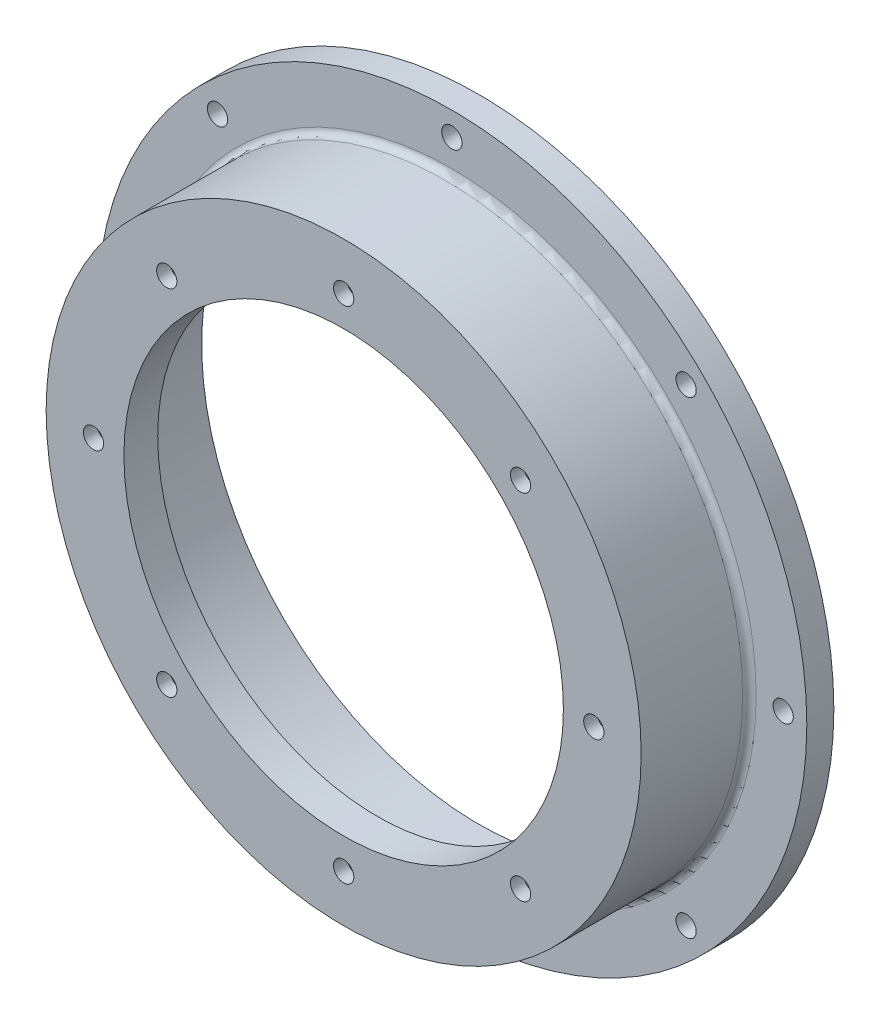
SolidWorks part; units mm, degrees
material "1.0503 (C45)"
ref_plane "Front Plane" through (0, 0, 0) normal (0, 0, 1) x (1, 0, 0)
ref_plane "Top Plane" through (0, 0, 0) normal (0, 1, 0) x (1, 0, 0)
ref_plane "Right Plane" through (0, 0, 0) normal (1, 0, 0) x (0, 0, -1)
sketch "Sketch1" plane through (0, 0, 0) normal (0, 0, 1) x (1, 0, 0)
  line L0 (0, 0) -> (0, 63.1981) construction
  circle A0 centre (0, 0) radius 52.5
  circle A1 centre (0, 0) radius 32.5
  circle A2 centre (0, 0) radius 41
  circle A3 centre (0, 0) radius 44
  point P2 (0, 49)
  point P3 (0, 37)
  point P5 (26.163, 26.163)
  point P6 (34.6482, 34.6482)
  point P8 (37, 0)
  point P9 (26.163, -26.163)
  point P10 (0, -37)
  point P11 (-26.163, -26.163)
  point P12 (-37, 0)
  point P13 (-26.163, 26.163)
  point P14 (0, 0)
  point P17 (49, 0)
  point P18 (34.6482, -34.6482)
  point P19 (0, -49)
  point P20 (-34.6482, -34.6482)
  point P21 (-49, 0)
  point P22 (-34.6482, 34.6482)
  point P23 (0, 0)
  dimension "D1" = 105
  dimension "D4" = 65
  dimension "82" = 82
  dimension "D8" = 88
  dimension "D2" = 37
  dimension "D5" = 49
  dimension "D3" = 8
  dimension "D6" = 8
extrude "Boss-Extrude1" add sketch "Sketch1" along normal blind 5 contours A1 A2 region at (-39.8403, 0, 0)
extrude "Boss-Extrude2" add sketch "Sketch1<4>" along normal blind 5 and the other way blind 15 contours A2 A3 | A3 A0 region at (-51.0151, 0, 0) region at (-42.7555, 0, 0)
sketch "Sketch1<4>" plane through (0, 0, 0) normal (0, 0, 1) x (1, 0, 0) same geometry as "Sketch1"
sketch "Sketch4" plane through (0, 0, 0) normal (0, 0, 1) x (1, 0, 0)
  line L0 (0, 0) -> (0, 63.1981) construction
  circle A0 centre (0, 0) radius 60
  circle A1 centre (0, 0) radius 37.5
  point P2 (0, 47)
  point P3 (0, 37)
  point P5 (26.163, 26.163)
  point P6 (33.234, 33.234)
  point P8 (37, 0)
  point P9 (26.163, -26.163)
  point P10 (0, -37)
  point P11 (-26.163, -26.163)
  point P12 (-37, 0)
  point P13 (-26.163, 26.163)
  point P14 (0, 0)
  point P17 (47, 0)
  point P18 (33.234, -33.234)
  point P19 (0, -47)
  point P20 (-33.234, -33.234)
  point P21 (-47, 0)
  point P22 (-33.234, 33.234)
  point P23 (0, 0)
  dimension "D1" = 120
  dimension "D4" = 75
  dimension "D2" = 37
  dimension "D5" = 47
  dimension "D3" = 8
  dimension "D6" = 8
sketch "Sketch7" plane through (0, 0, 0) normal (0, 0, 1) x (1, 0, 0)
  line L0 (0, 0) -> (0, 63.1981) construction
  circle A0 centre (0, 0) radius 60
  circle A1 centre (0, 0) radius 37.5
  circle A2 centre (0, 37) radius 3.5
  circle A3 centre (26.163, 26.163) radius 3.5
  circle A4 centre (37, 0) radius 3.5
  circle A5 centre (26.163, -26.163) radius 3.5
  circle A6 centre (0, -37) radius 3.5
  circle A7 centre (-26.163, -26.163) radius 3.5
  circle A8 centre (-37, 0) radius 3.5
  circle A9 centre (-26.163, 26.163) radius 3.5
  point P2 (0, 47)
  point P3 (0, 37)
  point P5 (26.163, 26.163)
  point P6 (33.234, 33.234)
  point P8 (37, 0)
  point P9 (26.163, -26.163)
  point P10 (0, -37)
  point P11 (-26.163, -26.163)
  point P12 (-37, 0)
  point P13 (-26.163, 26.163)
  point P14 (0, 0)
  point P17 (47, 0)
  point P18 (33.234, -33.234)
  point P19 (0, -47)
  point P20 (-33.234, -33.234)
  point P21 (-47, 0)
  point P22 (-33.234, 33.234)
  point P23 (0, 0)
  point P40 (0, 0)
  dimension "D1" = 120
  dimension "D4" = 75
  dimension "D7" = 7
  dimension "D2" = 37
  dimension "D5" = 47
  dimension "D3" = 8
  dimension "D6" = 8
  dimension "D8" = 8
hole_wizard "Ø3.0mm Dowel Hole1" positions "Sketch8" profile "Sketch9" hole size "Ø3.0" standard "ISO" end condition through all
sketch "Sketch8" plane through (0, 0, 0) normal (0, 0, -1) x (-1, 0, 0)
  point P0 (-26.163, 26.163)
  point P3 (0, 37)
  point P6 (26.163, 26.163)
  point P9 (37, 0)
  point P12 (-37, 0)
  point P15 (0, -37)
  point P18 (26.163, -26.163)
  point P21 (-26.163, -26.163)
sketch "Sketch9" plane through (26.163, 26.163, 0) normal (1, 0, 0) x (0, 1, 0)
  line L0 (0, 0) -> (0, 5)
  line L1 (0, 5) -> (1.5, 5)
  line L2 (1.5, 5) -> (1.5, 0.025)
  line L3 (1.5, 0.025) -> (1.525, 0)
  line L5 (1.525, 0) -> (0, 0)
  line L6 (-1.5, 0.025) -> (-1.525, 0) construction
  line L11 (0, -6.35) -> (0, 107.95) construction
  dimension "Thru Hole Dia." = 3
  dimension "Thru Hole Depth" = 5
  dimension "Near C'Sink Dia." = 3.05
  dimension "Near C'Sink Angle" = 90
extrude "Cut-Extrude1" cut sketch "Sketch7" along normal blind 3 contours A1 A3 | A1 A3 | A1 L0 A2 | L0 A1 A2 | L0 A2 A1 | A2 L0 A1 | A1 A9 | A1 A9 | A1 A8 | A1 A8 | A1 A7 | A1 A7 | A1 A4 | A1 A4 | A1 A5 | A1 A5 | A1 A6 | A1 A6 region at (-1.5071, 35.7529, 0) region at (1.5071, 35.7529, 0) region at (-1.4555, 38.7288, 0) region at (1.4555, 38.7288, 0) region at (-25.2811, 25.2811, 0) region at (-27.3854, 27.3854, 0) region at (27.3854, 27.3854, 0) region at (25.2811, 25.2811, 0) region at (-35.7529, 0, 0) region at (-38.7288, 0, 0) region at (38.7288, 0, 0) region at (35.7529, 0, 0) region at (-25.2811, -25.2811, 0) region at (-27.3854, -27.3854, 0) region at (27.3854, -27.3854, 0) region at (25.2811, -25.2811, 0) region at (0, -35.7529, 0) region at (0, -38.7288, 0)
ref_plane "Plane1" through (0, 0, -15) normal (0, 0, -1) x (-1, 0, 0)
sketch "Sketch10" plane through (0, 0, -15) normal (0, 0, -1) x (-1, 0, 0)
  line L0 (0, 0) -> (0, 63.1981) construction
  circle A0 centre (0, 0) radius 60
  circle A1 centre (0, 0) radius 37.5
  point P2 (0, 49)
  point P3 (0, 37)
  point P5 (26.163, 26.163)
  point P6 (34.6482, 34.6482)
  point P8 (37, 0)
  point P9 (26.163, -26.163)
  point P10 (0, -37)
  point P11 (-26.163, -26.163)
  point P12 (-37, 0)
  point P13 (-26.163, 26.163)
  point P14 (0, 0)
  point P17 (49, 0)
  point P18 (34.6482, -34.6482)
  point P19 (0, -49)
  point P20 (-34.6482, -34.6482)
  point P21 (-49, 0)
  point P22 (-34.6482, 34.6482)
  point P23 (0, 0)
  dimension "D1" = 120
  dimension "D4" = 75
  dimension "D2" = 37
  dimension "D5" = 49
  dimension "D3" = 8
  dimension "D6" = 8
hole_wizard "Ø3.0mm Dowel Hole2" positions "Sketch11" profile "Sketch12" hole size "Ø3.0" standard "KS" end condition through all
sketch "Sketch11" plane through (0, 0, -15) normal (0, 0, -1) x (-1, 0, 0)
  point P0 (0, 49)
  point P3 (34.6482, 34.6482)
  point P6 (-34.6482, 34.6482)
  point P9 (-49, 0)
  point P12 (-34.6482, -34.6482)
  point P15 (49, 0)
  point P18 (34.6482, -34.6482)
  point P21 (0, -49)
sketch "Sketch12" plane through (0, 49, -15) normal (1, 0, 0) x (0, 1, 0)
  line L0 (0, 0) -> (0, 20)
  line L1 (0, 20) -> (1.5, 20)
  line L2 (1.5, 20) -> (1.5, 0.025)
  line L3 (1.5, 0.025) -> (1.525, 0)
  line L5 (1.525, 0) -> (0, 0)
  line L6 (-1.5, 0.025) -> (-1.525, 0) construction
  line L11 (0, -6.35) -> (0, 107.95) construction
  dimension "Thru Hole Dia." = 3
  dimension "Thru Hole Depth" = 20
  dimension "Near C'Sink Dia." = 3.05
  dimension "Near C'Sink Angle" = 90
ref_plane "Plane2" through (0, 0, 5) normal (0, 0, 1) x (1, 0, 0)
sketch "Sketch13" plane through (0, 0, 5) normal (0, 0, 1) x (1, 0, 0)
  line L0 (0, 0) -> (0, 63.1981) construction
  circle A0 centre (0, 0) radius 52.5
  circle A1 centre (0, 0) radius 32.5
  circle A2 centre (0, 0) radius 41
  circle A3 centre (0, 0) radius 44
  point P2 (0, 49)
  point P3 (0, 37)
  point P5 (26.163, 26.163)
  point P6 (34.6482, 34.6482)
  point P8 (37, 0)
  point P9 (26.163, -26.163)
  point P10 (0, -37)
  point P11 (-26.163, -26.163)
  point P12 (-37, 0)
  point P13 (-26.163, 26.163)
  point P14 (0, 0)
  point P17 (49, 0)
  point P18 (34.6482, -34.6482)
  point P19 (0, -49)
  point P20 (-34.6482, -34.6482)
  point P21 (-49, 0)
  point P22 (-34.6482, 34.6482)
  point P23 (0, 0)
  dimension "D1" = 105
  dimension "D4" = 65
  dimension "82" = 82
  dimension "D8" = 88
  dimension "D2" = 37
  dimension "D5" = 49
  dimension "D3" = 8
  dimension "D6" = 8
extrude "Cut-Extrude2" cut sketch "Sketch13" against normal blind 16 contours A3 A0 region at (-51.0151, 0, 5)
fillet "Fillet1" radius 0.5 1 edges at (41, 0, 0)
fillet "Fillet2" radius 1 1 edges at (44, 0, -11)
